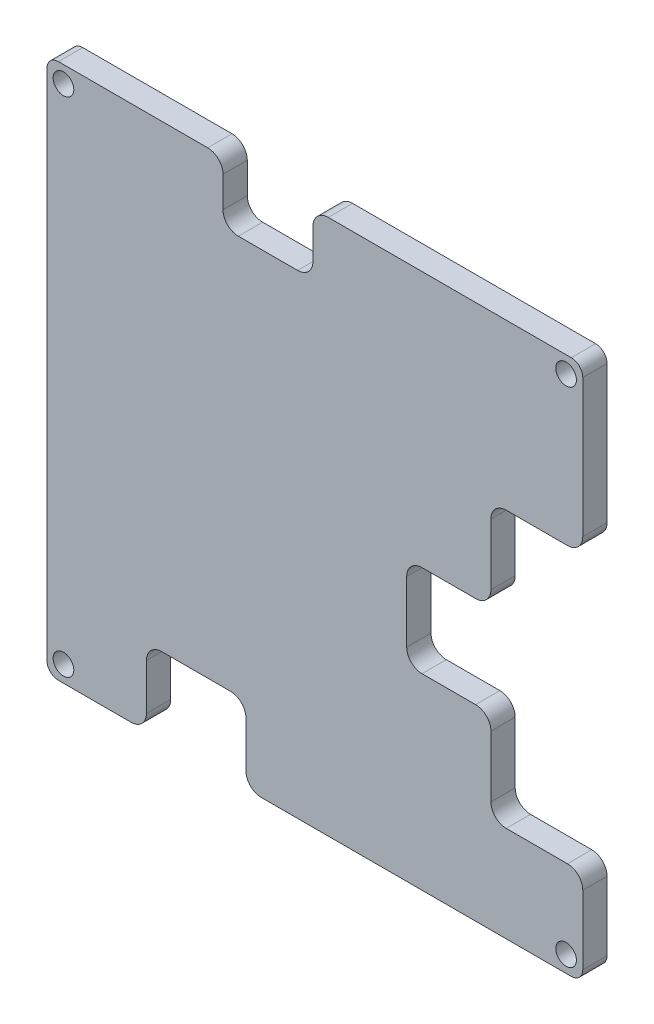
SolidWorks part; units mm, degrees
ref_plane "Front Plane" through (0, 0, 0) normal (0, 0, 1) x (1, 0, 0)
ref_plane "Top Plane" through (0, 0, 0) normal (0, 1, 0) x (1, 0, 0)
ref_plane "Right Plane" through (0, 0, 0) normal (1, 0, 0) x (0, 0, -1)
sketch "Sketch1" plane through (0, 0, 0) normal (0, 0, 1) x (1, 0, 0)
  line L1 (-35, 35) -> (35, 35)
  line L2 (-35, 35) -> (-35, -35)
  line L3 (-35, -35) -> (35, -35)
  line L4 (35, 35) -> (35, -35)
  line L5 (-35, 35) -> (35, -35) construction
  line L6 (-35, -35) -> (35, 35) construction
  circle A0 centre (-32.84, 32.82) radius 1.35
  circle A2 centre (-32.84, -32.84) radius 1.35
  circle A3 centre (32.82, -32.84) radius 1.35
  circle A4 centre (32.82, 32.82) radius 1.35
  point P0 (0, 0)
  dimension "D5" = 2.7
  dimension "D7" = 2.7
  dimension "D9" = 2.7
  dimension "D12" = 2.7
  dimension "D1" = 70
  dimension "D2" = 70
  dimension "D3" = 2.16
  dimension "D4" = 2.16
  dimension "D6" = 65.66
  dimension "D8" = 65.66
  dimension "D10" = 65.66
  dimension "D11" = 65.66
extrude "Boss-Extrude1" add sketch "Sketch1" along normal blind 3.175
fillet "Fillet1" radius 1.5 4 edges at (35, 35, 1.5875) (35, -35, 1.5875) (-35, -35, 1.5875) (-35, 35, 1.5875)
sketch "Sketch2" plane through (0, 0, 0) normal (0, 0, -1) x (-1, 0, 0)
  line L0 (0, 0) -> (35, 0) construction
  line L1 (35, 33.5) -> (35, -33.5) construction
  line L2 (0, 0) -> (0, 35) construction
  line L3 (-33.5, 35) -> (33.5, 35) construction
  line L18 (-35, 13.5) -> (-23, 13.5)
  line L19 (-35, -33.5) -> (-35, 33.5) construction
  line L20 (-23, 13.5) -> (-23, 1.5)
  line L21 (-23, 1.5) -> (-12, 1.5)
  line L22 (-12, 1.5) -> (-12, -10.5)
  line L23 (-12, -10.5) -> (-23, -10.5)
  line L24 (-23, -10.5) -> (-23, -22.5)
  line L25 (-23, -22.5) -> (-35, -22.5)
  line L26 (-35, 13.5) -> (-35, -22.5)
  line L27 (-33.5, 35) -> (33.5, 35) construction
  dimension "D1" = 21.5
  dimension "D2" = 12
  dimension "D3" = 12
  dimension "D4" = 12
  dimension "D5" = 12
  dimension "D6" = 12
  dimension "D7" = 11
extrude "Cut-Extrude1" cut sketch "Sketch2" against normal through all both and the other way through all
fillet "Fillet2" radius 2 8 edges at (23, 13.5, 1.5875) (12, -10.5, 1.5875) (12, 1.5, 1.5875) (23, -22.5, 1.5875) (35, -22.5, 1.5875) (35, 13.5, 1.5875) (23, -10.5, 1.5875) (23, 1.5, 1.5875)
sketch "Sketch3" plane through (0, 0, 0) normal (0, 0, -1) x (-1, 0, 0)
  line L0 (33.5, -35) -> (-33.5, -35) construction
  line L1 (22, -35) -> (9, -35)
  line L2 (22, -35) -> (22, -25)
  line L3 (22, -25) -> (9, -25)
  line L4 (9, -35) -> (9, -25)
  line L5 (-33.5, 35) -> (33.5, 35) construction
  line L6 (12, 35) -> (0.25, 35)
  line L7 (12, 35) -> (12, 27)
  line L8 (12, 27) -> (0.25, 27)
  line L9 (0.25, 35) -> (0.25, 27)
  line L10 (35, 33.5) -> (35, -33.5) construction
  line L11 (35, 33.5) -> (35, -33.5) construction
  dimension "D1" = 11.75
  dimension "D2" = 23
  dimension "D3" = 8
  dimension "D4" = 13
  dimension "D5" = 13
  dimension "D6" = 10
extrude "Cut-Extrude2" cut sketch "Sketch3" against normal through all both and the other way through all
fillet "Fillet3" radius 2 8 edges at (-9, -35, 1.5875) (-22, -35, 1.5875) (-22, -25, 1.5875) (-9, -25, 1.5875) (-12, 27, 1.5875) (-0.25, 27, 1.5875) (-0.25, 35, 1.5875) (-12, 35, 1.5875)
